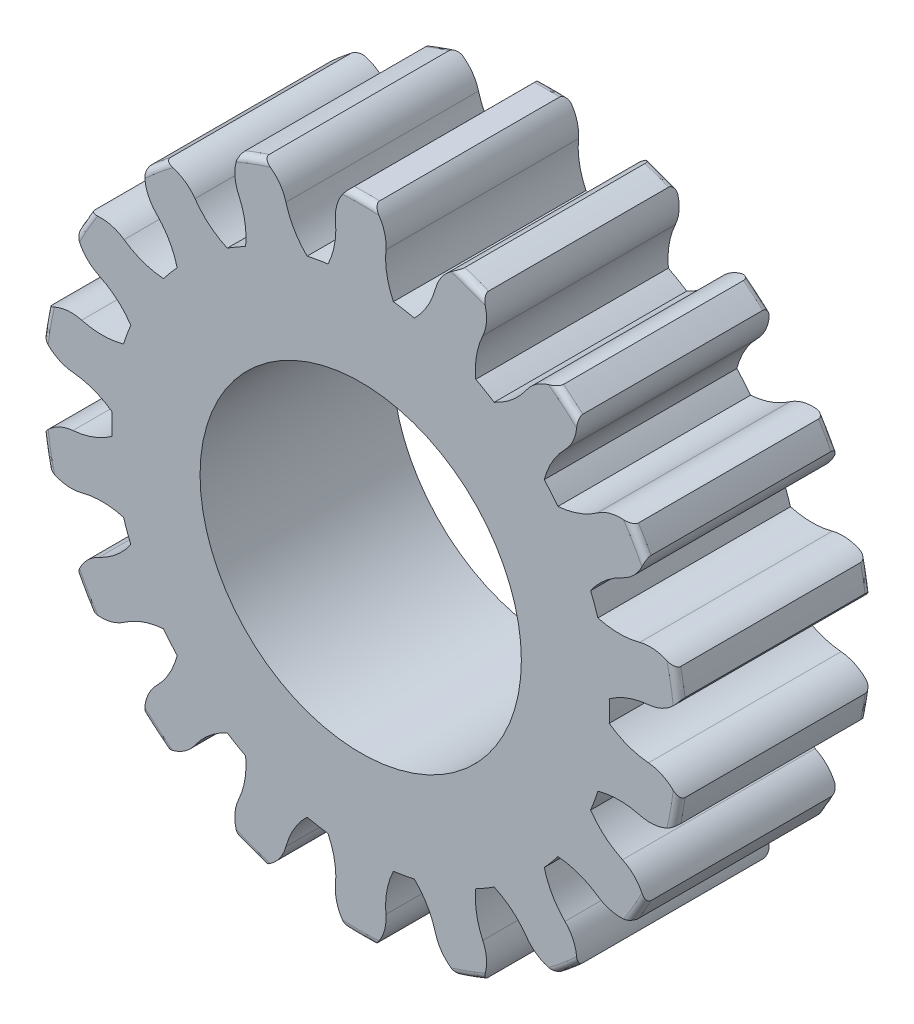
SolidWorks part; units mm, degrees
material "AISI 4130 Steel, annealed at 865C"
ref_plane "Front Plane" through (0, 0, 0) normal (0, 0, 1) x (1, 0, 0)
ref_plane "Top Plane" through (0, 0, 0) normal (0, 1, 0) x (1, 0, 0)
ref_plane "Right Plane" through (0, 0, 0) normal (1, 0, 0) x (0, 0, -1)
sketch "Sketch1" plane through (0, 0, 0) normal (0, 0, 1) x (1, 0, 0)
  circle A0 centre (0, 0) radius 18
  dimension "Pitch circcle" = 36
sketch "Sketch2" plane through (0, 0, 0) normal (0, 0, 1) x (1, 0, 0)
  circle A0 centre (0, 0) radius 15.5
  circle A1 centre (0, 0) radius 20
  circle A2 centre (0, 0) radius 18 construction
  circle A3 centre (0, 0) radius 10.01
  dimension "D1" = 20.02
  dimension "dedendum" = 2.5
  dimension "outercircle" = 2
extrude "Boss-Extrude1" add sketch "Sketch2" along normal mid plane 12 contours A0 A3 region at (-15.0616, 0, 0)
sketch "Sketch3" plane through (0, 0, 0) normal (0, 0, 1) x (1, 0, 0)
  line L0 (0, 0) -> (0, 30.1868) construction
  line L1 (1.5688, 20.5331) -> (1.5688, 28.4748) construction
  line L2 (-1.5688, 17.9315) -> (-8.1087, 92.6833) construction
  line L3 (0, -6.6437) -> (0, 6.6437) construction
  arc A0 (1.5688, 17.9315) -> (-1.5688, 17.9315) centre (0, 0) ccw
  circle A1 centre (0, 0) radius 18 construction
  circle A2 centre (0, 0) radius 15.5 construction
  circle A3 centre (0, 0) radius 20 construction
  arc A4 (-0.7852, 19.9846) -> (0.7852, 19.9846) centre (0, 0) cw
  arc A5 (-2.0361, 15.3657) -> (2.0361, 15.3657) centre (0, 0) cw
  circle A6 centre (0, 0) radius 15.5 construction
  arc A7 (-2.0361, 15.3657) -> (-1.5688, 17.9315) centre (-6.4848, 17.5014) ccw
  arc A8 (-1.5688, 17.9315) -> (-0.7852, 19.9846) centre (0.938, 18.1508) cw
  arc A9 (2.0361, 15.3657) -> (1.5688, 17.9315) centre (6.4848, 17.5014) cw
  arc A10 (1.5688, 17.9315) -> (0.7852, 19.9846) centre (-0.938, 18.1508) ccw
  point P7 (0, 18)
  dimension "D3" = 0
  dimension "CIrcpitch" = 3.1416
  dimension "D1" = 4.0841
  dimension "D2" = 1.5708
extrude "Boss-Extrude2" add sketch "Sketch3" along normal mid plane 12 contours A8 A7 A5 A9 A10 A4
fillet "Fillet1" radius 0.3927 2 edges at (0, 20, -6) (0, 20, 6)
pattern_circular "CirPattern1" count 18 over 360 about axis through (0, 0, 6) along (0, 0, 1) of "Boss-Extrude2", "Fillet1"
equation "\"Module\"= \"Global Module\"'diameter/nTeeth"
equation "\"nTeeth\"= \"3nteeth\"'number of teeth"
equation "\"PressureAngle\"= \"GlobalPressureAngle\""
equation "\"GearWidth\"= \"Module\" * 6'Thickness of gear"
equation "\"Pitch_Dia\"= \"Module\" * \"nTeeth\"'effectie diameter of gear"
equation "\"Addendum\"= \"Module\""
equation "\"Dedendumm\"= \"Module\" * 1.25"
equation "\"Base_Dia\"= \"Pitch_Dia\" * cos ( \"PressureAngle\" )"
equation "\"Pitch circcle@Sketch1\"=\"Pitch_Dia\""
equation "\"dedendum@Sketch2\"=\"Dedendumm\""
equation "\"outercircle@Sketch2\"=\"Addendum\""
equation "\"D1@Boss-Extrude1\"=\"GearWidth\""
equation "\"CircPitch\"= ( 3.1415926 * \"Pitch_Dia\" ) / ( \"nTeeth\" * 2 )"
equation "\"CIrcpitch@Sketch3\" = \"CircPitch\""
equation "\"D1@CirPattern1\"=\"nTeeth\""
equation "\"Shaft Dia\"=20"
equation "\"D1@Sketch2\"=\"Shaft Dia\"*\"Shaft Apllicator\"?\""
equation "\"FilletR\"= \"CircPitch\" / ( 2 * 4 )"
equation "\"D1@Boss-Extrude2\"=\"GearWidth\""
equation "\"Has Shaft?\"= 1'0 no /1 yes"
equation "\"Shaft Apllicator\"= \"Has Shaft?\" + 0.001"
equation "\"D1@Sketch3\"=\"CircPitch\"*1.3"
equation "\"D2@Sketch3\"=\"CircPitch\"*0.5"
equation "\"D1@Fillet1\"=\"FilletR\""
equation "\"Global Module\"= 2'Compatibility Number"
equation "\"3nteeth\"= 18'number of teeth in Gear3"
equation "\"GlobalPressureAngle\"= 10"
